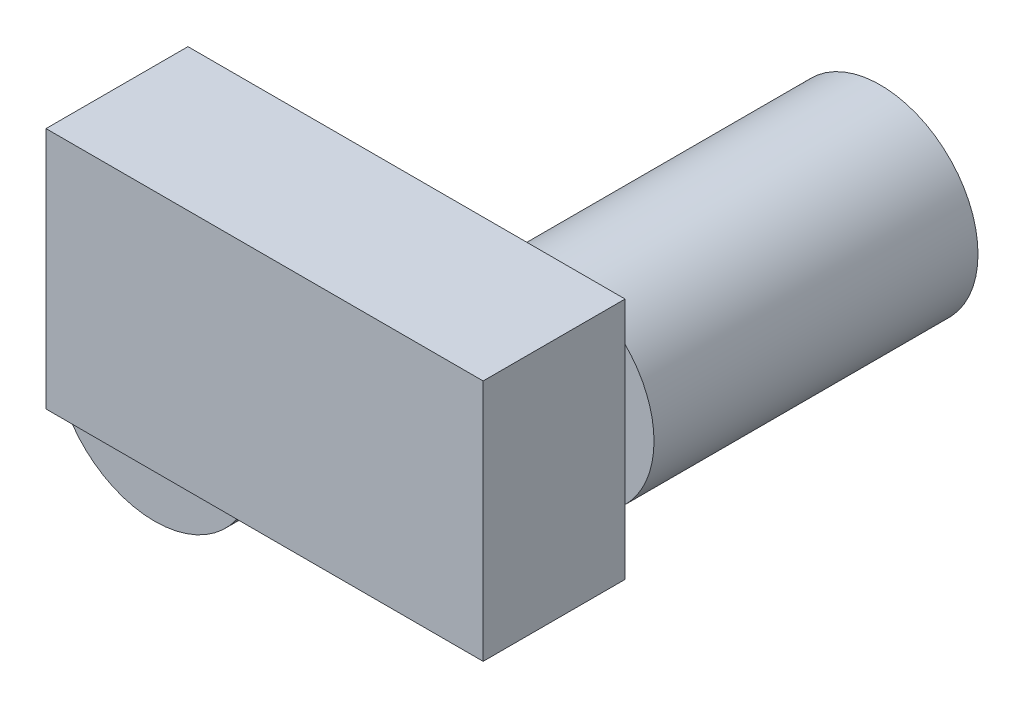
SolidWorks part; units mm, degrees
note: The reader was unsure of these and kept them because the rebuilt part matched: shared geometry of "Sketch1<17>", "Sketch2<6>".
ref_plane "Front Plane" through (0, 0, 0) normal (0, 0, 1) x (1, 0, 0)
ref_plane "Top Plane" through (0, 0, 0) normal (0, 1, 0) x (1, 0, 0)
ref_plane "Right Plane" through (0, 0, 0) normal (1, 0, 0) x (0, 0, -1)
sketch "Sketch1" plane through (0, 0, 0) normal (0, 0, 1) x (1, 0, 0)
  line L1 (-65.7028, -6.2338) -> (23.9847, -6.2338)
  line L2 (-65.7028, -6.2338) -> (-65.7028, 39.3831)
  line L3 (-65.7028, 39.3831) -> (23.9847, 39.3831)
  line L4 (23.9847, -6.2338) -> (23.9847, 39.3831)
  circle A0 centre (-43.4799, 0) radius 19.5
  circle A1 centre (-21.1862, 17.1814) radius 21.15
  circle A2 centre (9.0802, 18.5374) radius 19
  circle A3 centre (9.0802, 18.5374) radius 9.25
  circle A4 centre (-43.4799, 0) radius 19.537
  circle A5 centre (-21.1862, 17.1814) radius 8.5
  circle A6 centre (-21.1862, 17.1814) radius 3
  circle A7 centre (-43.4799, 0) radius 3
  circle A8 centre (9.0802, 18.5374) radius 3.3
extrude "Extrude13" add sketch "Sketch1" against normal blind 63
extrude "Extrude15" add sketch "Sketch1<17>" along normal blind 17
sketch "Sketch1<17>" plane through (0, 0, 0) normal (0, 0, 1) x (1, 0, 0) same geometry as "Sketch1"
sketch "Sketch2" plane through (0, 0, 0) normal (0, 0, 1) x (1, 0, 0)
  circle A0 centre (-21.0414, 14.5841) radius 21.15
  circle A1 centre (-21.0414, 14.5841) radius 8.5
  circle A2 centre (-45.03, 0) radius 19.5
  circle A3 centre (-45.03, 0) radius 3
  circle A4 centre (-21.0414, 14.5841) radius 3
extrude "Extrude18" add sketch "Sketch2" along normal blind 24
extrude "Cut-Extrude1" cut sketch "Sketch2<6>" along normal blind 14.38
sketch "Sketch2<6>" plane through (0, 0, 0) normal (0, 0, 1) x (1, 0, 0) same geometry as "Sketch2"
sketch "Sketch7" plane through (0, 0, 0) normal (0, 0, 1) x (1, 0, 0)
  line L3 (-62.5414, 39.6696) -> (22.4586, 39.6696)
  line L4 (-62.5414, 39.6696) -> (-62.5414, -7.5508)
  line L5 (-62.5414, -7.5508) -> (22.4586, -7.5508)
  line L6 (22.4586, 39.6696) -> (22.4586, -7.5508)
extrude "Extrude21" add sketch "Sketch7" along normal blind 27.6
